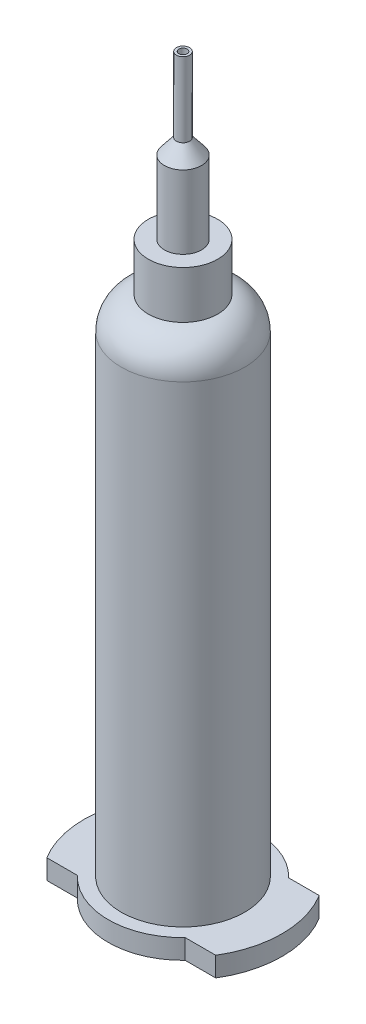
SolidWorks part; units mm, degrees
ref_plane "Front Plane" through (0, 0, 0) normal (0, 0, 1) x (1, 0, 0)
ref_plane "Top Plane" through (0, 0, 0) normal (0, 1, 0) x (1, 0, 0)
ref_plane "Right Plane" through (0, 0, 0) normal (1, 0, 0) x (0, 0, -1)
ref_axis "Axis1" through (-33.0333, 0, 0) along (1, 0, 0)
ref_axis "Axis2" through (0, 24.5224, 0) along (0, -1, 0)
ref_axis "Axis3" through (0, 0, -52.9538) along (0, 0, 1)
sketch "Sketch2" plane through (0, 0, 0) normal (0, 0, 1) x (1, 0, 0)
  line L8 (0, 55.88) -> (0, -55.88)
  line L9 (0, 55.88) -> (1, 55.88)
  line L10 (1, 55.88) -> (1, 44.53)
  line L11 (1, 44.53) -> (2.825, 42.2448)
  line L12 (2.825, 42.2448) -> (2.825, 31.12)
  line L13 (2.825, 31.12) -> (5.275, 31.12)
  line L14 (5.275, 31.12) -> (5.275, 23.88)
  line L15 (5.275, 23.88) -> (9.4, 23.88)
  line L16 (9.4, 23.88) -> (9.4, -52.88)
  line L17 (9.4, -52.88) -> (15.075, -52.88)
  line L18 (15.075, -52.88) -> (15.075, -55.88)
  line L19 (15.075, -55.88) -> (0, -55.88)
  point P2 (0, 0)
  dimension "D2" = 1
  dimension "D3" = 11.35
  dimension "D4" = 2.825
  dimension "D5" = 5.275
  dimension "D6" = 9.4
  dimension "D7" = 32
  dimension "D8" = 24.76
  dimension "D9" = 3
  dimension "D10" = 15.075
  dimension "D11" = 76.76
revolve "Revolve1" add sketch "Sketch2" angle 360 about axis through (0, 24.5224, 0) along (0, -1, 0) region at (4.5621, -11.6886, 0)
fillet "Fillet1" radius 5 1 edges at (0, 23.88, 9.4)
sketch "Sketch3" plane through (0, -52.88, 0) normal (0, 1, 0) x (1, 0, 0)
  line L0 (-12.8546, 7.875) -> (-8.2082, 7.875)
  line L1 (8.2082, 7.875) -> (12.8546, 7.875)
  line L2 (-111.883, 0) -> (111.883, 0) construction
  line L3 (-12.8546, -7.875) -> (-8.2082, -7.875)
  line L4 (8.2082, -7.875) -> (12.8546, -7.875)
  circle A0 centre (0, 0) radius 15.075 construction
  arc A1 (-8.2082, 7.875) -> (8.2082, 7.875) centre (0, 0) cw
  arc A2 (-12.8546, 7.875) -> (12.8546, 7.875) centre (0, 0) cw
  arc A3 (-8.2082, -7.875) -> (8.2082, -7.875) centre (0, 0) ccw
  arc A4 (-12.8546, -7.875) -> (12.8546, -7.875) centre (0, 0) ccw
  dimension "D2" = 11.375
  dimension "D1" = 15.75
extrude "Cut-Extrude1" cut sketch "Sketch3" against normal up to surface (3 mm away) up to face at (0, -55.88, 15.075)
sketch "Sketch4" plane through (0, -55.88, 0) normal (0, -1, 0) x (1, 0, 0)
  circle A0 centre (0, 0) radius 7.925
  dimension "D1" = 15.85
extrude "Cut-Extrude2" cut sketch "Sketch4" against normal blind 74
sketch "Sketch5" plane through (0, 55.88, 0) normal (0, 1, 0) x (1, 0, 0)
  circle A0 centre (0, 0) radius 0.6274
extrude "Cut-Extrude3" cut sketch "Sketch5" against normal blind 41
fillet "Fillet3" radius 10 1 edges at (0, 18.12, -0.6274)
ref_plane "Plane1" through (0, 18.12, 0) normal (0, 1, 0) x (1, 0, 0)
sketch "Sketch6" plane through (0, 18.12, 0) normal (0, 1, 0) x (1, 0, 0)
  circle A0 centre (0, 0) radius 7.925
  circle A1 centre (0, 0) radius 7.925 construction
extrude "Boss-Extrude2" add sketch "Sketch6" against normal blind 31 separate body
